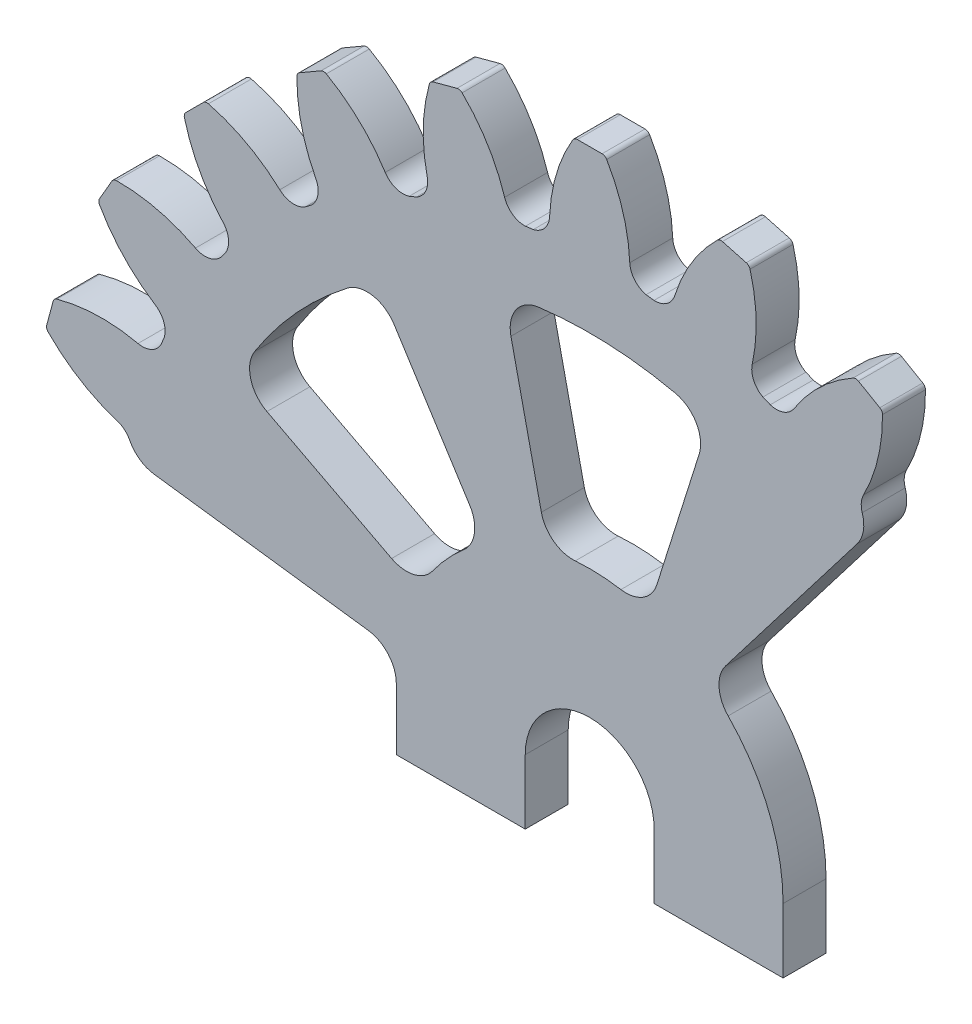
SolidWorks part; units mm, degrees
note: '?' marks a value the reader was unsure of.
ref_plane "Front" through (0, 0, 0) normal (0, 0, 1) x (1, 0, 0)
ref_plane "Top" through (0, 0, 0) normal (0, 1, 0) x (1, 0, 0)
ref_plane "Right" through (0, 0, 0) normal (1, 0, 0) x (0, 0, -1)
sketch "Sketch1" plane through (0, 0, 0) normal (0, 0, 1) x (1, 0, 0)
  line L0 (17.8313, 135.4426) -> (17.1518, 135.5303)
  line L1 (17.1518, 135.5303) -> (16.4718, 135.6147)
  line L2 (16.4718, 135.6147) -> (16.2604, 135.6453)
  line L3 (16.2604, 135.6453) -> (16.051, 135.6853)
  line L4 (16.051, 135.6853) -> (15.8446, 135.7346)
  line L5 (15.8446, 135.7346) -> (15.6419, 135.7926)
  line L6 (15.6419, 135.7926) -> (15.4439, 135.859)
  line L7 (15.4439, 135.859) -> (15.2509, 135.9332)
  line L8 (15.2509, 135.9332) -> (15.0638, 136.0145)
  line L9 (15.0638, 136.0145) -> (14.8827, 136.1025)
  line L10 (14.8827, 136.1025) -> (14.7082, 136.1963)
  line L11 (14.7082, 136.1963) -> (14.5404, 136.2955)
  line L12 (14.5404, 136.2955) -> (14.3796, 136.3992)
  line L13 (14.3796, 136.3992) -> (14.2256, 136.507)
  line L14 (14.2256, 136.507) -> (14.0785, 136.6183)
  line L15 (14.0785, 136.6183) -> (13.9383, 136.7325)
  line L16 (13.9383, 136.7325) -> (13.8047, 136.8493)
  line L17 (13.8047, 136.8493) -> (13.6777, 136.9682)
  line L18 (13.6777, 136.9682) -> (13.5568, 137.0887)
  line L19 (13.5568, 137.0887) -> (13.442, 137.2107)
  line L20 (13.442, 137.2107) -> (13.333, 137.3338)
  line L21 (13.333, 137.3338) -> (13.2295, 137.4577)
  line L22 (13.2295, 137.4577) -> (13.1311, 137.5824)
  line L23 (13.1311, 137.5824) -> (13.0378, 137.7076)
  line L24 (13.0378, 137.7076) -> (12.9491, 137.8333)
  line L25 (12.9491, 137.8333) -> (12.8649, 137.9592)
  line L26 (12.8649, 137.9592) -> (12.7848, 138.0855)
  line L27 (12.7848, 138.0855) -> (12.7088, 138.2119)
  line L28 (12.7088, 138.2119) -> (12.6364, 138.3386)
  line L29 (12.6364, 138.3386) -> (12.5676, 138.4654)
  line L30 (12.5676, 138.4654) -> (12.4399, 138.7196)
  line L31 (12.4399, 138.7196) -> (12.324, 138.9746)
  line L32 (12.324, 138.9746) -> (12.2189, 139.2306)
  line L33 (12.2189, 139.2306) -> (12.1235, 139.488)
  line L34 (12.1235, 139.488) -> (12.037, 139.7472)
  line L35 (12.037, 139.7472) -> (11.9587, 140.0083)
  line L36 (11.9587, 140.0083) -> (11.8878, 140.272)
  line L37 (11.8878, 140.272) -> (11.8239, 140.5386)
  line L38 (11.8239, 140.5386) -> (11.7667, 140.8083)
  line L39 (11.7667, 140.8083) -> (11.7159, 141.0816)
  line L40 (11.7159, 141.0816) -> (11.671, 141.3588)
  line L41 (11.671, 141.3588) -> (11.6319, 141.6402)
  line L42 (11.6319, 141.6402) -> (11.5986, 141.9261)
  line L43 (11.5986, 141.9261) -> (11.5708, 142.2169)
  line L44 (11.5708, 142.2169) -> (11.5484, 142.5127)
  line L45 (11.5484, 142.5127) -> (11.5316, 142.8138)
  line L46 (11.5316, 142.8138) -> (11.5201, 143.1205)
  line L47 (11.5201, 143.1205) -> (11.514, 143.431)
  line L48 (11.514, 143.431) -> (11.5065, 143.7657)
  line L49 (11.5065, 143.7657) -> (11.492, 144.1009)
  line L50 (11.492, 144.1009) -> (11.4715, 144.4366)
  line L51 (11.4715, 144.4366) -> (11.4457, 144.7727)
  line L52 (11.4457, 144.7727) -> (11.415, 145.1092)
  line L53 (11.415, 145.1092) -> (11.3797, 145.4459)
  line L54 (11.3797, 145.4459) -> (11.3401, 145.783)
  line L55 (11.3401, 145.783) -> (11.2966, 146.1204)
  line L56 (11.2966, 146.1204) -> (11.2492, 146.458)
  line L57 (11.2492, 146.458) -> (11.1981, 146.7959)
  line L58 (11.1981, 146.7959) -> (11.1435, 147.1341)
  line L59 (11.1435, 147.1341) -> (11.0853, 147.4724)
  line L60 (11.0853, 147.4724) -> (11.024, 147.8109)
  line L61 (11.024, 147.8109) -> (10.9594, 148.1496)
  line L62 (10.9594, 148.1496) -> (10.8916, 148.4885)
  line L63 (10.8916, 148.4885) -> (10.8208, 148.8275)
  line L64 (10.8208, 148.8275) -> (10.6703, 149.5062)
  line L65 (10.6703, 149.5062) -> (10.5084, 150.1852)
  line L66 (10.5084, 150.1852) -> (10.3354, 150.8648)
  line L67 (10.3354, 150.8648) -> (10.1517, 151.5448)
  line L68 (10.1517, 151.5448) -> (9.9576, 152.2251)
  line L69 (9.9576, 152.2251) -> (9.7535, 152.9057)
  line L70 (9.7535, 152.9057) -> (9.5395, 153.5865)
  line L71 (9.5395, 153.5865) -> (9.3158, 154.2674)
  line L72 (9.3158, 154.2674) -> (9.0828, 154.9485)
  line L73 (9.0828, 154.9485) -> (8.8405, 155.6295)
  line L74 (8.8405, 155.6295) -> (8.589, 156.3106)
  line L75 (8.589, 156.3106) -> (8.3286, 156.9917)
  line L76 (8.3286, 156.9917) -> (8.0594, 157.6726)
  line L77 (8.0594, 157.6726) -> (7.7815, 158.3534)
  line L78 (7.7815, 158.3534) -> (7.4951, 159.0339)
  line L79 (7.4951, 159.0339) -> (7.2001, 159.7142)
  line L80 (7.2001, 159.7142) -> (6.8968, 160.3942)
  line L81 (6.8968, 160.3942) -> (6.5852, 161.0739)
  line L82 (6.5852, 161.0739) -> (6.2654, 161.7531)
  line L83 (6.2654, 161.7531) -> (5.9375, 162.432)
  line L84 (5.9375, 162.432) -> (5.6015, 163.1103)
  line L85 (5.6015, 163.1103) -> (5.2576, 163.7881)
  line L86 (5.2576, 163.7881) -> (4.9057, 164.4653)
  line L87 (4.9057, 164.4653) -> (4.5461, 165.1419)
  line L88 (4.5461, 165.1419) -> (3.4097, 165.1693)
  line L89 (3.4097, 165.1693) -> (2.2732, 165.1888)
  line L90 (2.2732, 165.1888) -> (1.1366, 165.2006)
  line L91 (1.1366, 165.2006) -> (0, 165.2045)
  line L92 (0, 165.2045) -> (-1.1366, 165.2006)
  line L93 (-1.1366, 165.2006) -> (-2.2732, 165.1888)
  line L94 (-2.2732, 165.1888) -> (-3.4097, 165.1693)
  line L95 (-3.4097, 165.1693) -> (-4.5461, 165.1419)
  line L96 (-4.5461, 165.1419) -> (-4.9057, 164.4653)
  line L97 (-4.9057, 164.4653) -> (-5.2576, 163.7881)
  line L98 (-5.2576, 163.7881) -> (-5.6015, 163.1103)
  line L99 (-5.6015, 163.1103) -> (-5.9375, 162.432)
  line L100 (-5.9375, 162.432) -> (-6.2654, 161.7531)
  line L101 (-6.2654, 161.7531) -> (-6.5852, 161.0739)
  line L102 (-6.5852, 161.0739) -> (-6.8968, 160.3942)
  line L103 (-6.8968, 160.3942) -> (-7.2001, 159.7142)
  line L104 (-7.2001, 159.7142) -> (-7.4951, 159.0339)
  line L105 (-7.4951, 159.0339) -> (-7.7815, 158.3534)
  line L106 (-7.7815, 158.3534) -> (-8.0594, 157.6726)
  line L107 (-8.0594, 157.6726) -> (-8.3286, 156.9917)
  line L108 (-8.3286, 156.9917) -> (-8.589, 156.3106)
  line L109 (-8.589, 156.3106) -> (-8.8405, 155.6295)
  line L110 (-8.8405, 155.6295) -> (-9.0828, 154.9485)
  line L111 (-9.0828, 154.9485) -> (-9.3158, 154.2674)
  line L112 (-9.3158, 154.2674) -> (-9.5395, 153.5865)
  line L113 (-9.5395, 153.5865) -> (-9.7535, 152.9057)
  line L114 (-9.7535, 152.9057) -> (-9.9576, 152.2251)
  line L115 (-9.9576, 152.2251) -> (-10.1517, 151.5448)
  line L116 (-10.1517, 151.5448) -> (-10.3354, 150.8648)
  line L117 (-10.3354, 150.8648) -> (-10.5084, 150.1852)
  line L118 (-10.5084, 150.1852) -> (-10.6703, 149.5062)
  line L119 (-10.6703, 149.5062) -> (-10.8208, 148.8275)
  line L120 (-10.8208, 148.8275) -> (-10.8916, 148.4885)
  line L121 (-10.8916, 148.4885) -> (-10.9594, 148.1496)
  line L122 (-10.9594, 148.1496) -> (-11.024, 147.8109)
  line L123 (-11.024, 147.8109) -> (-11.0853, 147.4724)
  line L124 (-11.0853, 147.4724) -> (-11.1435, 147.1341)
  line L125 (-11.1435, 147.1341) -> (-11.1981, 146.7959)
  line L126 (-11.1981, 146.7959) -> (-11.2492, 146.458)
  line L127 (-11.2492, 146.458) -> (-11.2966, 146.1204)
  line L128 (-11.2966, 146.1204) -> (-11.3401, 145.783)
  line L129 (-11.3401, 145.783) -> (-11.3797, 145.4459)
  line L130 (-11.3797, 145.4459) -> (-11.415, 145.1092)
  line L131 (-11.415, 145.1092) -> (-11.4457, 144.7727)
  line L132 (-11.4457, 144.7727) -> (-11.4715, 144.4366)
  line L133 (-11.4715, 144.4366) -> (-11.492, 144.1009)
  line L134 (-11.492, 144.1009) -> (-11.5065, 143.7657)
  line L135 (-11.5065, 143.7657) -> (-11.514, 143.431)
  line L136 (-11.514, 143.431) -> (-11.5201, 143.1205)
  line L137 (-11.5201, 143.1205) -> (-11.5316, 142.8138)
  line L138 (-11.5316, 142.8138) -> (-11.5484, 142.5127)
  line L139 (-11.5484, 142.5127) -> (-11.5708, 142.2169)
  line L140 (-11.5708, 142.2169) -> (-11.5986, 141.9261)
  line L141 (-11.5986, 141.9261) -> (-11.6319, 141.6402)
  line L142 (-11.6319, 141.6402) -> (-11.671, 141.3588)
  line L143 (-11.671, 141.3588) -> (-11.7159, 141.0816)
  line L144 (-11.7159, 141.0816) -> (-11.7667, 140.8083)
  line L145 (-11.7667, 140.8083) -> (-11.8239, 140.5386)
  line L146 (-11.8239, 140.5386) -> (-11.8878, 140.272)
  line L147 (-11.8878, 140.272) -> (-11.9587, 140.0083)
  line L148 (-11.9587, 140.0083) -> (-12.037, 139.7472)
  line L149 (-12.037, 139.7472) -> (-12.1235, 139.488)
  line L150 (-12.1235, 139.488) -> (-12.2189, 139.2306)
  line L151 (-12.2189, 139.2306) -> (-12.324, 138.9746)
  line L152 (-12.324, 138.9746) -> (-12.4399, 138.7196)
  line L153 (-12.4399, 138.7196) -> (-12.5676, 138.4654)
  line L154 (-12.5676, 138.4654) -> (-12.6364, 138.3386)
  line L155 (-12.6364, 138.3386) -> (-12.7088, 138.2119)
  line L156 (-12.7088, 138.2119) -> (-12.7848, 138.0855)
  line L157 (-12.7848, 138.0855) -> (-12.8649, 137.9592)
  line L158 (-12.8649, 137.9592) -> (-12.9491, 137.8333)
  line L159 (-12.9491, 137.8333) -> (-13.0378, 137.7076)
  line L160 (-13.0378, 137.7076) -> (-13.1311, 137.5824)
  line L161 (-13.1311, 137.5824) -> (-13.2295, 137.4577)
  line L162 (-13.2295, 137.4577) -> (-13.333, 137.3338)
  line L163 (-13.333, 137.3338) -> (-13.442, 137.2107)
  line L164 (-13.442, 137.2107) -> (-13.5568, 137.0887)
  line L165 (-13.5568, 137.0887) -> (-13.6777, 136.9682)
  line L166 (-13.6777, 136.9682) -> (-13.8047, 136.8493)
  line L167 (-13.8047, 136.8493) -> (-13.9383, 136.7325)
  line L168 (-13.9383, 136.7325) -> (-14.0785, 136.6183)
  line L169 (-14.0785, 136.6183) -> (-14.2256, 136.507)
  line L170 (-14.2256, 136.507) -> (-14.3796, 136.3992)
  line L171 (-14.3796, 136.3992) -> (-14.5404, 136.2955)
  line L172 (-14.5404, 136.2955) -> (-14.7082, 136.1963)
  line L173 (-14.7082, 136.1963) -> (-14.8827, 136.1025)
  line L174 (-14.8827, 136.1025) -> (-15.0638, 136.0145)
  line L175 (-15.0638, 136.0145) -> (-15.2509, 135.9332)
  line L176 (-15.2509, 135.9332) -> (-15.4439, 135.859)
  line L177 (-15.4439, 135.859) -> (-15.6419, 135.7926)
  line L178 (-15.6419, 135.7926) -> (-15.8446, 135.7346)
  line L179 (-15.8446, 135.7346) -> (-16.051, 135.6853)
  line L180 (-16.051, 135.6853) -> (-16.2604, 135.6453)
  line L181 (-16.2604, 135.6453) -> (-16.4718, 135.6147)
  line L182 (-16.4718, 135.6147) -> (-17.1518, 135.5303)
  line L183 (-17.1518, 135.5303) -> (-17.8313, 135.4426)
sketch "Sketch2" plane through (0, 0, 0) normal (0, 0, 1) x (1, 0, 0)
  line L0 (0, 0) -> (0, 362.4864) construction
  line L1 (-4.5461, 165.1419) -> (4.5461, 165.1419)
  line L2 (-17.8314, 135.4426) -> (0, 0) construction
  line L3 (17.8314, 135.4426) -> (17.8314, 110.0426)
  line L4 (17.8314, 110.0426) -> (-17.8314, 110.0426)
  line L5 (-17.8314, 110.0426) -> (-17.8314, 135.4426)
  line L6 (-17.1518, 135.5303) -> (-17.8313, 135.4426) construction
  arc A0 (-17.8314, 135.4426) -> (-11.8464, 141.3588) centre (-18.0264, 141.6253) ccw
  arc A1 (-11.8464, 141.3588) -> (-4.5461, 165.1419) centre (37.4738, 139.2317) cw
  arc A2 (11.8464, 141.3588) -> (4.5461, 165.1419) centre (-37.4738, 139.2317) ccw
  arc A3 (17.8314, 135.4426) -> (11.8464, 141.3588) centre (18.0264, 141.6253) cw
  point P25 (0, 165.1419)
  dimension "D1" = 7.5
  dimension "D2" = 25.4
sketch "Sketch3" plane through (0, 0, 0) normal (0, 0, 1) x (1, 0, 0)
  circle A0 centre (0, 0) radius 136.6114
extrude "Extrude1" add sketch "Sketch3" along normal blind 12.7
extrude "Extrude2" add sketch "Sketch2" along normal blind 12.7
fillet "Fillet2" radius 1.5875 2 edges at (4.5461, 165.1419, 6.35) (-4.5461, 165.1419, 6.35)
ref_axis "Axis1" through (0, 0, 12.7) along (0, 0, -1)?
pattern_circular "CirPattern1" count 24 over 360 about axis through (0, 0, 0) along (0, 0, 1) of "Extrude2", "Fillet2"
sketch "Sketch4" plane through (0, 0, 0) normal (0, 0, 1) x (1, 0, 0)
  line L0 (-268.2184, 35.3116) -> (0, 0)
  line L1 (0, 0) -> (164.69, 214.6281)
  line L4 (0, -6.985) -> (0, 6.985) construction
  arc A0 (164.69, 214.6281) -> (-268.2184, 35.3116) centre (0, 0) ccw construction
  dimension "D1" = 37.5
  dimension "D2" = 82.5
  dimension "D3" = 120
extrude "Cut-Extrude1" cut sketch "Sketch4" against normal through all and the other way through all flip side to cut
sketch "Sketch5" plane through (0, 0, 0) normal (0, 0, 1) x (1, 0, 0)
  circle A0 centre (0, 0) radius 19.05
  dimension "D1" = 38.1
extrude "Cut-Extrude2" cut sketch "Sketch5" along normal up to next
sketch "Sketch6" plane through (0, 0, 0) normal (0, 0, 1) x (1, 0, 0)
  line L0 (-19.05, 0) -> (-19.05, -19.05)
  line L1 (-18.887, 2.4865) -> (-135.4426, 17.8314) construction
  line L2 (-19.05, -19.05) -> (-57.15, -19.05)
  line L3 (83.1637, 108.3811) -> (11.5969, 15.1134) construction
  line L4 (-56.6611, 7.4596) -> (-18.887, 2.4865)
  line L5 (11.5969, 15.1134) -> (34.7907, 45.3401)
  line L6 (-57.15, -19.05) -> (57.15, -19.05) construction
  line L7 (-57.15, 0) -> (-57.15, -19.05)
  line L8 (57.15, 0) -> (57.15, -19.05)
  line L9 (19.05, 0) -> (19.05, -19.05)
  line L10 (19.05, -19.05) -> (57.15, -19.05)
  line L11 (-57.15, 0) -> (57.15, 0) construction
  circle A0 centre (0, 0) radius 19.05 construction
  arc A1 (-57.15, 0) -> (-56.6611, 7.4596) centre (0, 0) cw
  arc A2 (-19.05, 0) -> (-18.887, 2.4865) centre (0, 0) cw
  arc A3 (11.5969, 15.1134) -> (-18.887, 2.4865) centre (0, 0) ccw construction
  arc A4 (57.15, 0) -> (34.7907, 45.3401) centre (0, 0) ccw
  arc A5 (19.05, 0) -> (11.5969, 15.1134) centre (0, 0) ccw
  dimension "D1" = 38.1
  dimension "D2" = 7.5
extrude "Extrude3" add sketch "Sketch6" along normal blind 12.7
sketch "Sketch8" plane through (0, 0, 0) normal (0, 0, 1) x (1, 0, 0)
  line L0 (0, 0) -> (-104.2016, 54.2439) construction
  line L1 (0, 0) -> (35.3254, 112.0379) construction
  line L2 (-56.6611, 7.4596) -> (-135.4426, 17.8314) construction
  line L3 (83.1637, 108.3811) -> (34.7907, 45.3401) construction
  line L4 (-25.4262, 114.6904) -> (-12.3695, 55.7953)
  line L5 (-63.1193, 99.0774) -> (-30.7067, 48.1998)
  line L6 (-104.2016, 54.2439) -> (-50.6927, 26.3889)
  line L7 (35.3254, 112.0379) -> (17.1853, 54.5049)
  arc A0 (-50.6927, 26.3889) -> (17.1853, 54.5049) centre (0, 0) cw construction
  arc A1 (-104.2016, 54.2439) -> (35.3254, 112.0379) centre (0, 0) cw construction
  arc A2 (57.15, 0) -> (34.7907, 45.3401) centre (0, 0) ccw construction
  arc A3 (-50.6927, 26.3889) -> (-30.7067, 48.1998) centre (0, 0) cw
  arc A4 (17.1853, 54.5049) -> (-12.3695, 55.7953) centre (0, 0) ccw
  arc A5 (35.3254, 112.0379) -> (-25.4262, 114.6904) centre (0, 0) ccw
  arc A6 (-104.2016, 54.2439) -> (-63.1193, 99.0774) centre (0, 0) cw
  dimension "D3" = 117.475
  dimension "D1" = 20
  dimension "D2" = 20
  dimension "D5" = 30
  dimension "D6" = 30
  dimension "D7" = 20
extrude "Cut-Extrude5" cut sketch "Sketch8" along normal through all
fillet "Fillet1" radius 9.525 11 edges at (34.7907, 45.3401, 6.35) (-50.6927, 26.3889, 6.35) (-30.7067, 48.1998, 6.35) (-63.1193, 99.0774, 6.35) (-104.2016, 54.2439, 6.35) (-12.3695, 55.7953, 6.35) (17.1853, 54.5049, 6.35) (35.3254, 112.0379, 6.35) (-25.4262, 114.6904, 6.35) (-56.6611, 7.4596, 6.35) (-57.15, 0, 6.35)
sketch "Sketch9" plane through (0, 0, 0) normal (0, 0, 1) x (1, 0, 0)
  line L0 (83.1637, 108.3811) -> (40.1729, 52.3543) construction
  line L1 (79.0341, 102.9992) -> (83.8095, 109.2227)
  line L2 (80.5391, 111.7322) -> (83.8095, 109.2227)
  line L3 (-65.4317, 8.6143) -> (-135.4426, 17.8314) construction
  line L4 (-128.717, 16.9459) -> (-136.4944, 17.9698)
  line L5 (-135.9563, 22.0568) -> (-136.4944, 17.9698)
  arc A0 (79.0341, 102.9992) -> (80.5391, 111.7322) centre (71.4774, 108.7977) ccw
  arc A1 (80.9387, 116.4971) -> (82.229, 109.0919) centre (86.424, 113.6379) ccw construction
  arc A2 (-135.9563, 22.0568) -> (-128.717, 16.9459) centre (-127.4737, 26.3894) ccw
  arc A3 (-135.2843, 18.995) -> (-139.6082, 25.1436) centre (-141.4651, 19.2431) ccw construction
  dimension "D1" = 9.525
  dimension "D2" = 9.525
extrude "Cut-Extrude7" cut sketch "Sketch9" along normal blind 12.7
